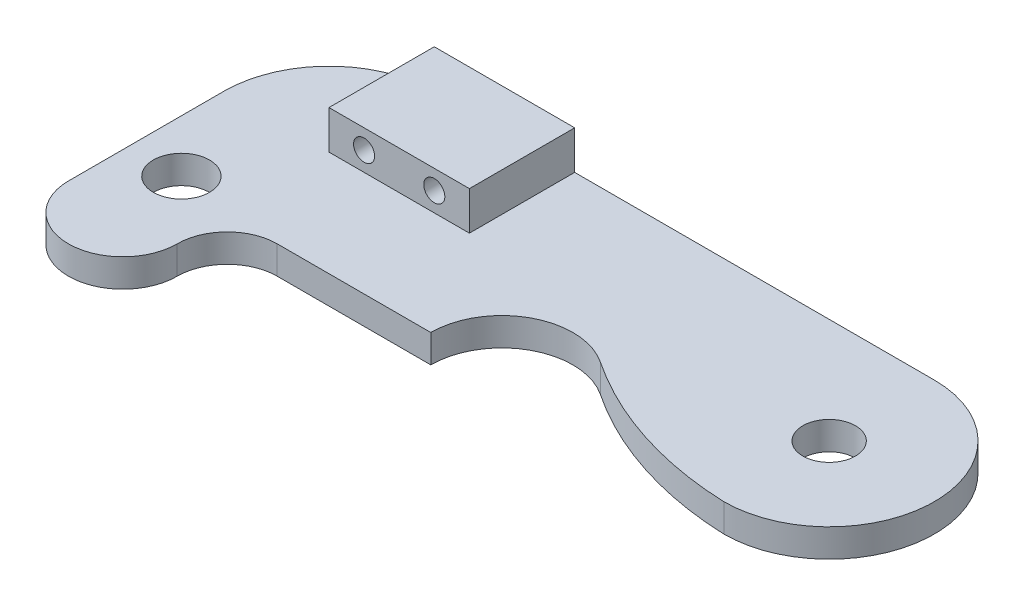
SolidWorks part; units mm, degrees
ref_plane "Front Plane" through (0, 0, 0) normal (0, 0, 1) x (1, 0, 0)
ref_plane "Top Plane" through (0, 0, 0) normal (0, 1, 0) x (1, 0, 0)
ref_plane "Right Plane" through (0, 0, 0) normal (1, 0, 0) x (0, 0, -1)
sketch "Sketch1" plane through (0, 0, 0) normal (0, 1, 0) x (1, 0, 0)
  line L15 (39.0719, -176.8025) -> (67.5719, -176.8025)
  line L17 (42.1221, -188.8025) -> (50.8721, -188.8025)
  line L21 (33.0721, -182.7525) -> (33.0721, -191.6525)
  line L22 (33.0721, -191.6525) -> (39.2721, -191.6525) construction
  line L24 (42.1221, -191.6525) -> (42.1221, -188.8025) construction
  line L25 (58.9721, -188.8025) -> (67.5719, -188.8025)
  line L26 (50.8721, -188.8025) -> (58.9721, -188.8025)
  arc A10 (67.5719, -188.8025) -> (67.5719, -176.8025) centre (67.5719, -182.8025) ccw
  arc A12 (39.0719, -176.8025) -> (33.0721, -182.7525) centre (39.0719, -182.8025) ccw
  arc A14 (42.1221, -188.8025) -> (39.2721, -191.6525) centre (42.1221, -191.6525) ccw
  arc A15 (58.9721, -188.8025) -> (50.8721, -188.8025) centre (54.9221, -188.8025) ccw
  arc A16 (33.0721, -191.6525) -> (39.2721, -191.6525) centre (36.1721, -191.6525) ccw
  circle A17 centre (36.0529, -188.1938) radius 1.6
  circle A18 centre (67.5719, -182.8025) radius 1.5
  circle A19 centre (36.0529, -188.1938) radius 1.6 construction
  dimension "D1" = 3.1
  dimension "D2" = 4.05
  dimension "D3" = 8.75
  dimension "D4" = 2.85
  dimension "D5" = 6
  dimension "D6" = 6
  dimension "D7" = 8.9
  dimension "D9" = 3
  dimension "D12" = 90
  dimension "D10" = 3.2
  dimension "D13" = 0
  dimension "D8" = 28.5
  dimension "D11" = 0
extrude "Boss-Extrude1" add sketch "Sketch1" along normal blind 1.6 contours L21 A16 A14 L17 A15 L25 A10 L15 A12 A18 A17 region at (51.7129, 0, 183.1937)
sketch "Sketch2" plane through (0, 1.6, 0) normal (0, 1, 0) x (1, 0, 0)
  line L1 (39.0719, -176.8025) -> (47.0719, -176.8025)
  line L2 (39.0719, -176.8025) -> (39.0719, -182.8025)
  line L3 (39.0719, -182.8025) -> (47.0719, -182.8025)
  line L4 (47.0719, -176.8025) -> (47.0719, -182.8025)
  dimension "D1" = 6
  dimension "D2" = 8
extrude "Boss-Extrude2" add sketch "Sketch2" along normal blind 2.2
sketch "Sketch3" plane through (0, 0, 176.8025) normal (0, 0, -1) x (-1, 0, 0)
  line L0 (-47.0719, 3.8) -> (-39.0719, 3.8) construction
  line L1 (-39.0719, 3.8) -> (-39.0719, 1.6) construction
  line L2 (-47.0719, 3.8) -> (-47.0719, 1.6) construction
  circle A0 centre (-45.0719, 2.7) radius 0.6
  circle A1 centre (-41.0719, 2.7) radius 0.6
  dimension "D5" = 1.2
  dimension "D6" = 1.2
  dimension "D1" = 1.1
  dimension "D2" = 1.1
  dimension "D3" = 2
  dimension "D4" = 2
extrude "Cut-Extrude1" cut sketch "Sketch3" against normal up to next
fillet "Fillet1" radius 20 1 edges at (58.9721, 0.8, 188.8025)
